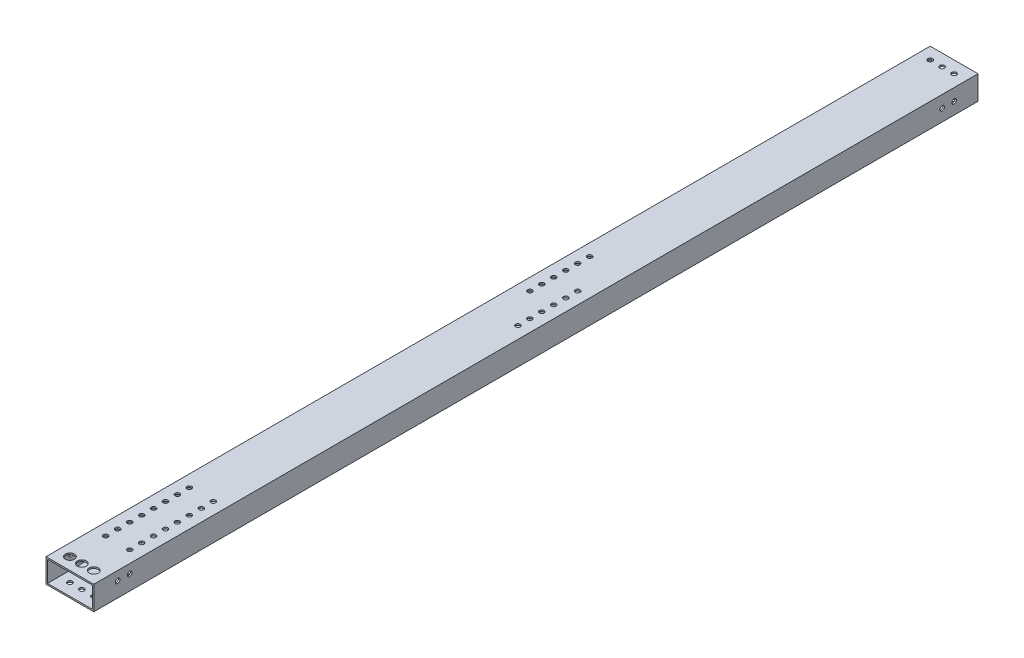
SolidWorks part; units mm, degrees
material "6061-T6 (SS)"
ref_plane "Front Plane" through (0, 0, 0) normal (0, 0, 1) x (1, 0, 0)
ref_plane "Top Plane" through (0, 0, 0) normal (0, 1, 0) x (1, 0, 0)
ref_plane "Right Plane" through (0, 0, 0) normal (1, 0, 0) x (0, 0, -1)
sketch "Sketch1" plane through (0, 0, 0) normal (0, 0, 1) x (1, 0, 0)
  line L0 (-23.8125, 11.1125) -> (23.8125, 11.1125)
  line L1 (-25.4, -12.7) -> (25.4, -12.7)
  line L2 (-25.4, -12.7) -> (-25.4, 12.7)
  line L3 (-25.4, 12.7) -> (25.4, 12.7)
  line L4 (25.4, -12.7) -> (25.4, 12.7)
  line L5 (-25.4, -12.7) -> (25.4, 12.7) construction
  line L6 (-25.4, 12.7) -> (25.4, -12.7) construction
  line L7 (23.8125, -11.1125) -> (23.8125, 11.1125)
  line L8 (-23.8125, -11.1125) -> (23.8125, -11.1125)
  line L9 (-23.8125, -11.1125) -> (-23.8125, 11.1125)
  point P0 (0, 0)
  dimension "D1" = 50.8
  dimension "D2" = 25.4
  dimension "D3" = 1.5875
extrude "Boss-Extrude1" add sketch "Sketch1" along normal mid plane 939.8
sketch "Sketch4" plane through (0, 12.7, 0) normal (0, 1, 0) x (1, 0, 0)
  line L0 (25.4, -469.9) -> (-25.4, -469.9) construction
  circle A0 centre (-12.7, -457.2) radius 4.826
  circle A1 centre (0, -457.2) radius 4.826
  circle A2 centre (12.7, -457.2) radius 4.826
  dimension "D1" = 9.652
  dimension "D2" = 12.7
  dimension "D3" = 12.7
  dimension "D4" = 12.7
extrude "Cut-Extrude3" cut sketch "Sketch4" against normal up to surface (1.5875 mm away) contours A0 | A1 | A2 region at (-12.7, 12.7, 457.2) region at (0, 12.7, 457.2) region at (12.7, 12.7, 457.2) up to face at (0, 11.1125, 0)
sketch "Sketch5" plane through (0, -12.7, 0) normal (0, -1, 0) x (1, 0, 0)
  circle A0 centre (-12.7, 457.2) radius 4.826 construction
  circle A1 centre (0, 457.2) radius 4.826 construction
  circle A2 centre (12.7, 457.2) radius 4.826 construction
  circle A3 centre (-12.7, 457.2) radius 4.826
  circle A4 centre (0, 457.2) radius 4.826
  circle A5 centre (12.7, 457.2) radius 4.826
  circle A6 centre (-12.7, 457.2) radius 2.5527
  circle A7 centre (0, 457.2) radius 2.5527
  circle A8 centre (12.7, 457.2) radius 2.5527
  dimension "D1" = 5.1054
extrude "Cut-Extrude4" cut sketch "Sketch5" against normal up to surface (1.5875 mm away) contours A8 | A7 | A6 region at (-12.7, -12.7, 457.2) region at (0, -12.7, 457.2) region at (12.7, -12.7, 457.2) up to face at (0, -11.1125, 0)
sketch "Sketch6" plane through (0, -12.7, 0) normal (0, -1, 0) x (1, 0, 0)
  line L0 (-25.4, -469.9) -> (25.4, -469.9) construction
  circle A0 centre (-12.7, -457.2) radius 2.5527
  circle A1 centre (0, -457.2) radius 2.5527
  circle A2 centre (12.7, -457.2) radius 2.5527
  dimension "D1" = 5.1054
  dimension "D2" = 12.7
  dimension "D3" = 12.7
  dimension "D4" = 12.7
extrude "Cut-Extrude5" cut sketch "Sketch6" against normal through all contours A2 | A1 | A0 region at (-12.7, -12.7, -457.2) region at (0, -12.7, -457.2) region at (12.7, -12.7, -457.2)
sketch "Sketch7" plane through (25.4, 0, 0) normal (1, 0, 0) x (0, 0, -1)
  line L0 (-469.9, -12.7) -> (-469.9, 12.7) construction
  line L2 (469.9, -12.7) -> (469.9, 12.7) construction
  line L3 (-469.9, -12.7) -> (469.9, -12.7) construction
  circle A0 centre (-457.2, 3.175) radius 2.4892
  circle A1 centre (-444.5, 3.175) radius 2.4892
  circle A2 centre (-431.8, 3.175) radius 2.4892
  circle A3 centre (-419.1, 3.175) radius 2.4892
  circle A4 centre (457.2, 0) radius 2.4892
  circle A5 centre (444.5, 0) radius 2.4892
  circle A6 centre (431.8, 0) radius 2.4892
  dimension "D1" = 4.9784
  dimension "D7" = 4.9784
  dimension "D8" = 12.7
  dimension "D2" = 12.7
  dimension "D3" = 12.7
  dimension "D4" = 12.7
  dimension "D5" = 12.7
  dimension "D6" = 15.875
  dimension "D9" = 12.7
  dimension "D10" = 12.7
  dimension "D11" = 12.7
extrude "Cut-Extrude6" cut sketch "Sketch7" against normal through all contours A6 | A5 | A1 | A2 region at (25.4, 3.175, 444.5) region at (25.4, 3.175, 431.8) region at (25.4, 0, -444.5) region at (25.4, 0, -431.8)
sketch "Sketch10" plane through (0, 12.7, 0) normal (0, 1, 0) x (1, 0, 0)
  line L1 (25.4, -469.9) -> (-25.4, -469.9) construction
  line L3 (-25.4, -469.9) -> (-25.4, 469.9) construction
  circle A0 centre (-12.7, -419.1) radius 2.4892
  circle A5 centre (12.7, -419.1) radius 2.4892
  circle A6 centre (-12.7, -406.4) radius 2.4892
  circle A7 centre (12.7, -406.4) radius 2.4892
  circle A8 centre (-12.7, -393.7) radius 2.4892
  circle A9 centre (12.7, -393.7) radius 2.4892
  circle A10 centre (-12.7, -381) radius 2.4892
  circle A11 centre (12.7, -381) radius 2.4892
  circle A12 centre (-12.7, -368.3) radius 2.4892
  circle A13 centre (12.7, -368.3) radius 2.4892
  circle A14 centre (-12.7, -355.6) radius 2.4892
  circle A15 centre (12.7, -355.6) radius 2.4892
  circle A16 centre (-12.7, -342.9) radius 2.4892
  circle A17 centre (12.7, -342.9) radius 2.4892
  circle A18 centre (-12.7, -330.2) radius 2.4892
  circle A19 centre (12.7, -330.2) radius 2.4892
  circle A20 centre (-12.7, 31.75) radius 2.4892
  circle A21 centre (12.7, -6.35) radius 2.4892
  circle A22 centre (-12.7, 44.45) radius 2.4892
  circle A23 centre (12.7, 6.35) radius 2.4892
  circle A24 centre (-12.7, 57.15) radius 2.4892
  circle A25 centre (12.7, 19.05) radius 2.4892
  circle A26 centre (-12.7, 69.85) radius 2.4892
  circle A27 centre (12.7, 31.75) radius 2.4892
  circle A28 centre (-12.7, 82.55) radius 2.4892
  circle A29 centre (12.7, 44.45) radius 2.4892
  circle A30 centre (-12.7, 95.25) radius 2.4892
  circle A31 centre (12.7, 57.15) radius 2.4892
  dimension "D1" = 25.4
  dimension "D3" = 4.9784
  dimension "D2" = 12.7
  dimension "D4" = 50.8
  dimension "D5" = 12.7
  dimension "D6" = 323.85
  dimension "D7" = 361.95
  dimension "D8" = 12.7
  dimension "D9" = 6
extrude "Cut-Extrude8" cut sketch "Sketch10" against normal through all
